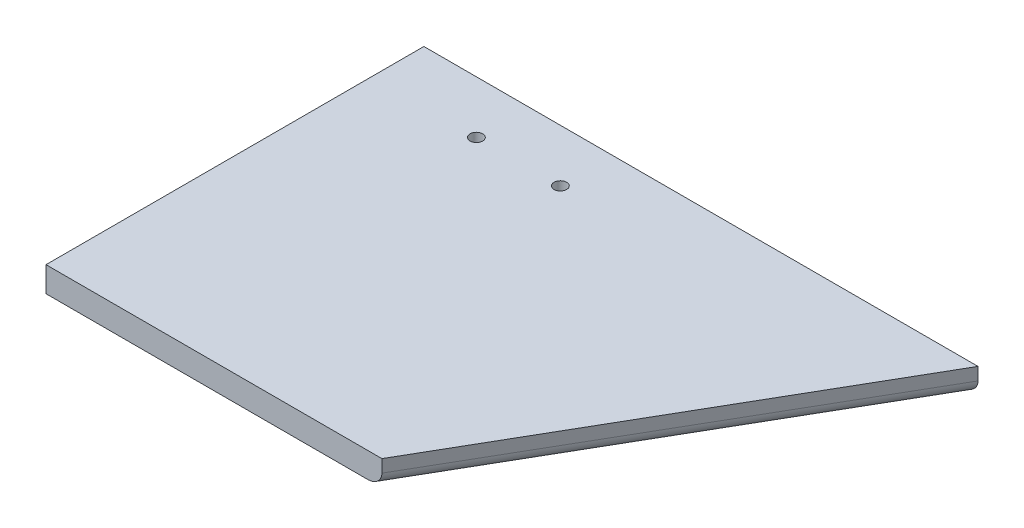
SolidWorks part; units mm, degrees
ref_plane "Front" through (0, 0, 0) normal (0, 0, 1) x (1, 0, 0)
ref_plane "Top" through (0, 0, 0) normal (0, 1, 0) x (1, 0, 0)
ref_plane "Right" through (0, 0, 0) normal (1, 0, 0) x (0, 0, -1)
sketch "Sketch1" plane through (0, 0, 0) normal (0, 1, 0) x (1, 0, 0)
  line L0 (0, 0) -> (51.9615, 90)
  line L1 (0, 0) -> (-80, 0)
  line L3 (0, 90) -> (-80, 90)
  line L4 (-80, 0) -> (-80, 90)
  line L5 (51.9615, 90) -> (0, 90)
  dimension "D1" = 80
  dimension "D2" = 90
  dimension "D3" = 120
extrude "Boss-Extrude1" add sketch "Sketch1" along normal blind 6
fillet "Fillet1" radius 3 1 edges at (25.9808, 0, -45)
sketch "Sketch2" plane through (0, 6, 0) normal (0, 1, 0) x (1, 0, 0)
  line L0 (-80, 90) -> (-80, 0) construction
  line L1 (51.9615, 90) -> (-80, 90) construction
  circle A0 centre (-55, 77.5) radius 1.5
  circle A1 centre (-35, 77.5) radius 1.5
  dimension "D1" = 3
  dimension "D2" = 20
  dimension "D3" = 25
  dimension "D4" = 12.5
extrude "Cut-Extrude1" cut sketch "Sketch2" against normal through all
